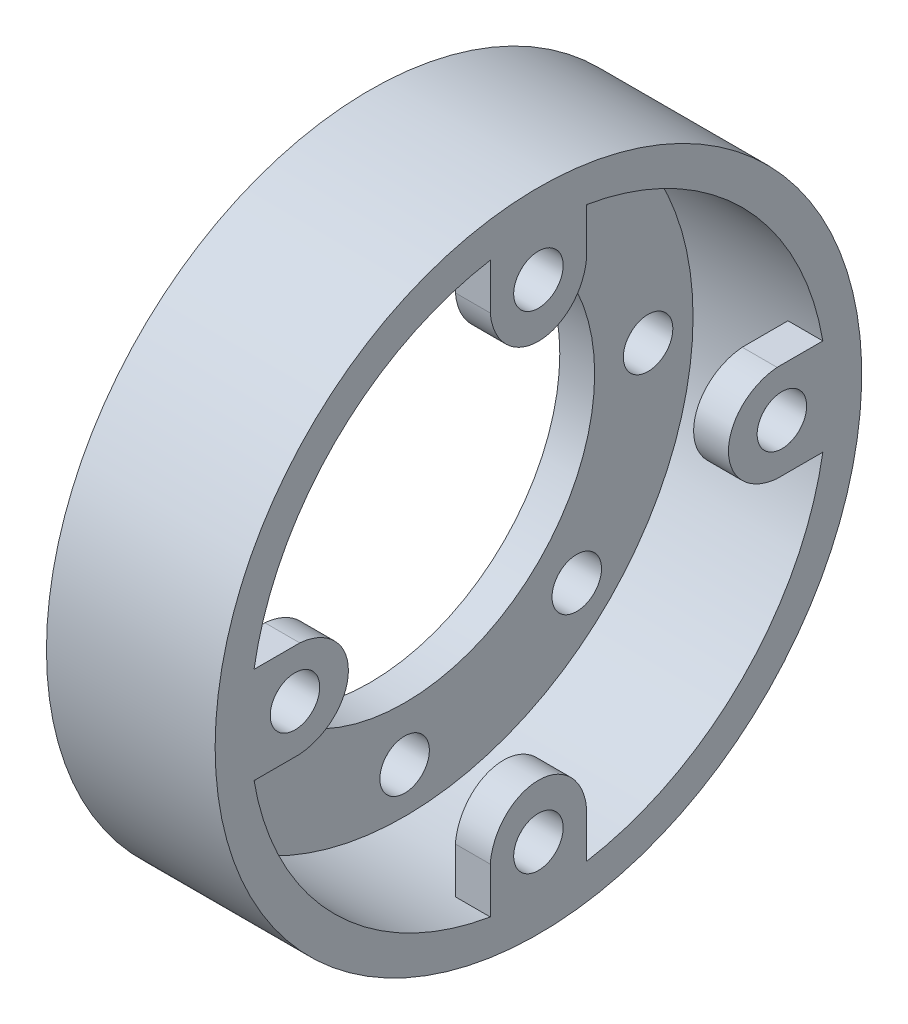
SolidWorks part; units mm, degrees
ref_plane "Front Plane" through (0, 0, 0) normal (0, 0, 1) x (1, 0, 0)
ref_plane "Top Plane" through (0, 0, 0) normal (0, 1, 0) x (1, 0, 0)
ref_plane "Right Plane" through (0, 0, 0) normal (1, 0, 0) x (0, 0, -1)
sketch "Sketch1" plane through (0, 0, 0) normal (1, 0, 0) x (0, 0, -1)
  circle A0 centre (0, 0) radius 73.025
  circle A1 centre (0, 0) radius 65.151
  circle A2 centre (0, 0) radius 42.926
  dimension "D1" = 146.05
  dimension "D2" = 7.874
  dimension "D3" = 85.852
extrude "Boss-Extrude2" add sketch "Sketch1" along normal blind 7.874 contours A2 | A1
extrude "Boss-Extrude3" add sketch "Sketch1<5>" along normal blind 38.1 contours A0 A1 region at (0, 0, 70.9595)
sketch "Sketch1<5>" plane through (0, 0, 0) normal (1, 0, 0) x (0, 0, -1) same geometry as "Sketch1"
sketch "Sketch24" plane through (7.874, 0, 0) normal (1, 0, 0) x (0, 0, -1)
  line L0 (0, 0) -> (0, 13.5628) construction
  circle A0 centre (0, 0) radius 54.991 construction
  circle A1 centre (0, 0) radius 65.151 construction
  circle A2 centre (0, 54.991) radius 5.588
  dimension "D1" = 10.16
extrude "Cut-Extrude1" cut sketch "Sketch24" against normal blind 38.1
pattern_circular "CirPattern3" count 8 over 360 about axis through (7.874, 0, 0) along (1, 0, 0) of "Cut-Extrude1"
ref_plane "Plane1" through (38.1, 0, 0) normal (1, 0, 0) x (0, 0, -1)
sketch "Sketch34" plane through (38.1, 0, 0) normal (1, 0, 0) x (0, 0, -1)
  line L0 (10.8813, -53.9037) -> (10.8813, -64.2359)
  line L1 (-10.8813, -53.9037) -> (-10.8813, -64.2359)
  circle A0 centre (0, 0) radius 42.926 construction
  circle A1 centre (0, 0) radius 54.991 construction
  circle A2 centre (0, 0) radius 65.151 construction
  circle A4 centre (0, 0) radius 65.151
  arc A5 (-10.8813, -64.2359) -> (10.8813, -64.2359) centre (0, 0) ccw
  ellipse E0 centre (0, -54.991) end of major axis (0, -67.056) minor radius 10.9258 (10.8813, -53.9037) -> (-10.8813, -53.9037) ccw
  dimension "D1" = 0
extrude "Boss-Extrude7" add sketch "Sketch34" against normal blind 7.874 contours E0 L1 A5 L0
sketch "Sketch35" plane through (38.1, 0, 0) normal (1, 0, 0) x (0, 0, -1)
  circle A0 centre (0, -54.991) radius 5.588
  circle A1 centre (0, 0) radius 54.991 construction
extrude "Cut-Extrude2" cut sketch "Sketch35" against normal through all contours A0
pattern_circular "CirPattern9" count 4 over 360 about axis through (38.1, 0, 0) along (-1, 0, 0) of "Boss-Extrude7", "Cut-Extrude2"
